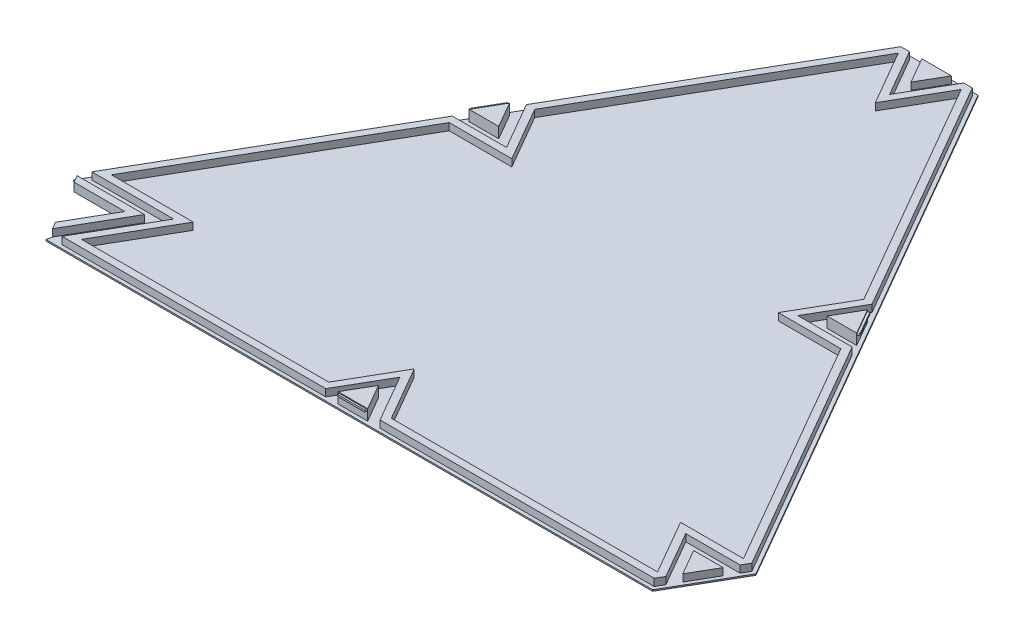
SolidWorks part; units mm, degrees
ref_plane "Front Plane" through (0, 0, 0) normal (0, 0, 1) x (1, 0, 0)
ref_plane "Top Plane" through (0, 0, 0) normal (0, 1, 0) x (1, 0, 0)
ref_plane "Right Plane" through (0, 0, 0) normal (1, 0, 0) x (0, 0, -1)
sketch "Sketch1" plane through (0, 0, 0) normal (0, 1, 0) x (1, 0, 0)
  line L17 (-84.5662, 18.8923) -> (-84.5662, 18.3923) construction
  line L24 (-89.7106, 9.9821) -> (-89.2776, 10.2321) construction
  line L25 (-79.4219, 9.9821) -> (-79.8549, 10.2321) construction
  line L27 (-84.5662, 2.0718) -> (-75.1436, 18.3923)
  line L28 (-93.9889, 18.3923) -> (-75.1436, 18.3923)
  line L29 (-2.5, 5.4019) -> (-2.067, 5.1519) construction
  line L58 (2.5, 5.4019) -> (2.067, 5.1519) construction
  line L59 (0, 1.0718) -> (0, 1.5718) construction
  line L65 (-4.134, 1.5718) -> (4.134, 1.5718)
  line L69 (0, 8.7321) -> (4.134, 1.5718)
  line L71 (-4.134, 1.5718) -> (0, 8.7321)
  line L79 (87.2106, 14.3122) -> (87.2106, 13.8122) construction
  line L81 (84.7106, 9.9821) -> (85.1436, 10.2321) construction
  line L135 (89.7106, 9.9821) -> (89.2776, 10.2321) construction
  line L138 (83.0766, 13.8122) -> (91.3446, 13.8122)
  line L146 (87.2106, 6.6519) -> (91.3446, 13.8122)
  line L149 (83.0766, 13.8122) -> (87.2106, 6.6519)
  line L157 (47.5718, 92.1288) -> (48.0048, 91.8788) construction
  line L158 (52.5718, 92.1288) -> (52.1388, 91.8788) construction
  line L160 (50.0718, 87.7987) -> (50.0718, 88.2987) construction
  line L161 (45.9378, 88.2987) -> (54.2058, 88.2987)
  line L162 (50.0718, 95.4589) -> (54.2058, 88.2987)
  line L163 (45.9378, 88.2987) -> (50.0718, 95.4589)
  line L164 (0, 165.3653) -> (0, 164.8653) construction
  line L165 (-2.5, 161.0352) -> (-2.067, 161.2852) construction
  line L166 (2.5, 161.0352) -> (2.067, 161.2852) construction
  line L167 (-4.134, 164.8653) -> (4.134, 164.8653)
  line L168 (0, 157.7051) -> (4.134, 164.8653)
  line L169 (-4.134, 164.8653) -> (0, 157.7051)
  line L170 (-52.5718, 92.1288) -> (-52.1388, 91.8788) construction
  line L171 (-47.5718, 92.1288) -> (-48.0048, 91.8788) construction
  line L172 (-50.0718, 87.7987) -> (-50.0718, 88.2987) construction
  line L173 (-54.2058, 88.2987) -> (-45.9378, 88.2987)
  line L174 (-50.0718, 95.4589) -> (-45.9378, 88.2987)
  line L175 (-54.2058, 88.2987) -> (-50.0718, 95.4589)
  line L176 (-76.5352, 10.9821) -> (-76.1021, 10.7321) construction
  line L177 (-69.9474, 21.3923) -> (-81.3908, 1.5718)
  line L178 (-3.6547, 7.4019) -> (-4.0877, 7.6519) construction
  line L179 (0, 14.7321) -> (-7.5981, 1.5718)
  line L180 (-7.5981, 1.5718) -> (-81.3908, 1.5718)
  line L181 (3.6547, 7.4019) -> (4.0877, 7.6519) construction
  line L182 (82.4012, 9.9821) -> (81.9682, 9.7321) construction
  line L183 (0, 14.7321) -> (7.5981, 1.5718)
  line L184 (85.3111, 2.3619) -> (84.878, 2.6119) construction
  line L185 (7.5981, 1.5718) -> (84.2776, 1.5718)
  line L186 (85.4785, 3.6519) -> (84.2776, 1.5718)
  line L187 (77.8805, 16.8122) -> (85.4785, 3.6519)
  line L188 (86.0559, 16.3122) -> (86.0559, 16.8122) construction
  line L189 (94.1101, 17.6022) -> (93.6771, 17.8522) construction
  line L190 (77.8805, 16.8122) -> (93.0766, 16.8122)
  line L191 (94.2776, 18.8923) -> (93.0766, 16.8122)
  line L192 (75.5407, 52.3455) -> (75.1077, 52.0955) construction
  line L193 (55.9378, 85.2987) -> (94.2776, 18.8923)
  line L194 (48.3397, 85.2987) -> (48.3397, 83.2987) construction
  line L195 (40.7417, 85.2987) -> (55.9378, 85.2987)
  line L196 (45.2624, 92.1288) -> (44.8294, 92.3788) construction
  line L197 (29.6029, 131.9121) -> (29.1699, 131.6621) construction
  line L198 (10, 164.8653) -> (48.3397, 98.4589)
  line L199 (40.7417, 85.2987) -> (48.3397, 98.4589)
  line L200 (8.799, 165.3653) -> (8.799, 164.8653) construction
  line L201 (7.5981, 164.8653) -> (10, 164.8653)
  line L202 (3.6547, 159.0352) -> (4.0877, 158.7852) construction
  line L203 (7.5981, 164.8653) -> (0, 151.7051)
  line L204 (-8.799, 165.3653) -> (-8.799, 164.8653) construction
  line L205 (-3.6547, 159.0352) -> (-4.0877, 158.7852) construction
  line L206 (-29.6029, 131.9121) -> (-29.1699, 131.6621) construction
  line L207 (-48.3397, 98.4589) -> (-10, 164.8653)
  line L208 (-10, 164.8653) -> (-7.5981, 164.8653)
  line L209 (0, 151.7051) -> (-7.5981, 164.8653)
  line L210 (-45.2624, 92.1288) -> (-44.8294, 92.3788) construction
  line L211 (-48.3397, 98.4589) -> (-40.7417, 85.2987)
  line L212 (-48.3397, 85.2987) -> (-48.3397, 83.2987) construction
  line L213 (-74.9634, 53.3455) -> (-74.5303, 53.0955) construction
  line L214 (-92.8342, 21.3923) -> (-55.9378, 85.2987)
  line L215 (-55.9378, 85.2987) -> (-40.7417, 85.2987)
  line L216 (-82.2568, 20.8923) -> (-82.2568, 21.3923) construction
  line L217 (-92.8342, 21.3923) -> (-69.9474, 21.3923)
  line L218 (-44.7831, 1.0718) -> (-44.7831, 0.5718) construction
  line L219 (-84.8549, 0.5718) -> (84.8549, 0.5718)
  line L220 (-89.7106, 9.9821) -> (-90.1436, 9.7321) construction
  line L222 (0, 165.3653) -> (0, 165.8653) construction
  line L223 (10.5774, 165.8653) -> (-10.5774, 165.8653)
  line L224 (-95.4323, 18.8923) -> (-10.5774, 165.8653)
  line L225 (52.5718, 92.1288) -> (53.0048, 92.3788) construction
  line L226 (95.4323, 18.8923) -> (10.5774, 165.8653)
  line L227 (89.7106, 9.9821) -> (90.1436, 9.7321) construction
  line L228 (84.8549, 0.5718) -> (95.4323, 18.8923)
  line L229 (-84.5662, 18.3923) -> (-84.5662, 16.3923) construction
  line L230 (-79.8549, 10.2321) -> (-81.587, 11.2321) construction
  line L232 (-89.2776, 10.2321) -> (-87.5455, 11.2321) construction
  line L235 (-95.4323, 18.8923) -> (-93.9889, 18.3923)
  line L236 (-84.8549, 0.5718) -> (-84.5662, 2.0718)
  line L238 (-92.8342, 16.3923) -> (-78.6077, 16.3923)
  line L239 (-78.6077, 16.3923) -> (-85.7209, 4.0718)
  line L240 (-93.9889, 18.3923) -> (-92.8342, 16.3923)
  line L241 (-85.7209, 4.0718) -> (-84.5662, 2.0718)
  line L242 (-44.4944, 1.5718) -> (-44.4944, 3.5718) construction
  line L243 (-75.6691, 11.4821) -> (-73.9371, 10.4821) construction
  line L244 (-77.9267, 3.5718) -> (-66.4833, 23.3923)
  line L245 (-77.9267, 3.5718) -> (-8.7528, 3.5718)
  line L246 (-3.799, 8.1519) -> (-5.5311, 9.1519) construction
  line L247 (-8.7528, 3.5718) -> (0, 18.7321)
  line L248 (4.0877, 7.6519) -> (5.8198, 8.6519) construction
  line L249 (45.9378, 1.5718) -> (45.9378, 3.5718) construction
  line L250 (0, 18.7321) -> (8.7528, 3.5718)
  line L251 (81.9682, 9.7321) -> (80.2361, 8.7321) construction
  line L252 (45.9378, 3.5718) -> (8.7528, 3.5718)
  line L253 (74.4164, 18.8122) -> (83.2154, 3.5718)
  line L254 (45.9378, 3.5718) -> (83.2154, 3.5718)
  line L255 (85.4785, 16.8122) -> (85.4785, 18.8122) construction
  line L256 (74.4164, 18.8122) -> (92.0144, 18.8122)
  line L257 (75.1077, 52.0955) -> (73.3756, 51.0955) construction
  line L258 (44.8294, 92.3788) -> (43.0973, 93.3788) construction
  line L259 (54.7831, 83.2987) -> (92.0144, 18.8122)
  line L260 (54.7831, 83.2987) -> (37.2776, 83.2987)
  line L261 (46.0303, 98.4589) -> (37.2776, 83.2987)
  line L262 (29.1699, 131.6621) -> (27.4378, 130.6621) construction
  line L263 (46.0303, 98.4589) -> (8.799, 162.9455)
  line L264 (4.0877, 158.7852) -> (5.8198, 157.7852) construction
  line L265 (0, 147.7051) -> (8.799, 162.9455)
  line L266 (-3.218, 157.2789) -> (-4.9501, 156.2789) construction
  line L267 (-8.799, 162.9455) -> (0, 147.7051)
  line L268 (-29.1699, 131.6621) -> (-27.4378, 130.6621) construction
  line L269 (-8.799, 162.9455) -> (-46.0303, 98.4589)
  line L270 (-44.5407, 91.8788) -> (-42.8087, 92.8788) construction
  line L271 (-46.0303, 98.4589) -> (-37.2776, 83.2987)
  line L272 (-54.7831, 83.2987) -> (-37.2776, 83.2987)
  line L273 (-72.465, 56.6729) -> (-70.7329, 55.6729) construction
  line L274 (-54.7831, 83.2987) -> (-89.3701, 23.3923)
  line L275 (-81.3908, 21.3923) -> (-81.3908, 23.3923) construction
  line L276 (-89.3701, 23.3923) -> (-66.4833, 23.3923)
  point P9 (-89.2776, 10.2321)
  point P12 (-79.8549, 10.2321)
  point P15 (-84.5662, 18.3923)
  point P21 (0, 1.5718)
  point P24 (2.067, 5.1519)
  point P27 (-2.067, 5.1519)
  point P32 (87.2106, 13.8122)
  point P36 (89.2776, 10.2321)
  point P41 (85.1436, 10.2321)
  point P48 (50.0718, 88.2987)
  point P49 (-84.5662, 16.3923)
  point P51 (50.0718, 88.2987)
  point P54 (52.1388, 91.8788)
  point P58 (48.0048, 91.8788)
  point P64 (-81.587, 11.2321)
  point P68 (-87.5455, 11.2321)
  point P74 (0, 164.8653)
  point P76 (-73.9371, 10.4821)
  point P81 (-44.4944, 3.5718)
  point P84 (-5.5311, 9.1519)
  point P87 (5.8198, 8.6519)
  point P89 (2.067, 161.2852)
  point P95 (80.2361, 8.7321)
  point P97 (-2.067, 161.2852)
  point P105 (85.4785, 18.8122)
  point P106 (-50.0718, 88.2987)
  point P109 (-50.0718, 88.2987)
  point P114 (-48.0048, 91.8788)
  point P118 (48.3397, 83.2987)
  point P119 (-52.1388, 91.8788)
  point P123 (-76.1021, 10.7321)
  point P131 (-4.0877, 7.6519)
  point P138 (4.0877, 7.6519)
  point P144 (84.878, 2.6119)
  point P146 (81.9682, 9.7321)
  point P151 (86.0559, 16.8122)
  point P154 (93.6771, 17.8522)
  point P156 (75.1077, 52.0955)
  point P157 (27.4378, 130.6621)
  point P168 (44.8294, 92.3788)
  point P172 (8.799, 164.8653)
  point P176 (4.0877, 158.7852)
  point P184 (-8.799, 164.8653)
  point P187 (-29.1699, 131.6621)
  point P191 (-44.8294, 92.3788)
  point P198 (-74.5303, 53.0955)
  point P204 (-82.2568, 21.3923)
  point P208 (-90.1436, 9.7321)
  point P212 (0, 165.8653)
  point P214 (0, 165.8653)
  point P217 (53.0048, 92.3788)
  point P218 (5.8198, 157.7852)
  point P220 (90.1436, 9.7321)
  point P226 (-27.4378, 130.6621)
  point P230 (-42.8087, 92.8788)
  point P231 (-42.8087, 92.8788)
  point P237 (-81.3908, 23.3923)
  dimension "D1" = 0.5
  dimension "D2" = 0.5
extrude "Boss-Extrude1" add sketch "Sketch1" along normal blind 2.38 contours L214 L217 L177 L180 L179 L183 L185 L186 L187 L190 L191 L193 L195 L199 L198 L201 L203 L209 L208 L207 L211 L215 | L239 L241 L27 L28 L240 L238 | L138 L146 L149 | L167 L168 L169 region at (-84.9277, 0, -3.1964) region at (-81.3908, 0, -21.6407)
extrude "Boss-Extrude4" add sketch "Sketch1<8>" along normal blind 0.38 contours L219 L228 L226 L223 L224 L173 L175 L174 L161 L163 L162 L65 L71 L69 L28 L27 L149 L138 L146 L169 L167 L168 L217 L214 L215 L211 L207 L208 L209 L203 L201 L198 L199 L195 L193 L191 L190 L187 L186 L185 L183 L179 | L276 L244 L245 L247 L250 L252 L254 L253 L256 L259 L260 L261 L263 L265 L267 L269 L271 L272 L274 region at (-77.6683, 0, -8.9696)
sketch "Sketch1<8>" plane through (0, 0, 0) normal (0, 1, 0) x (1, 0, 0) same geometry as "Sketch1"
extrude "Boss-Extrude5" add sketch "Sketch1<9>" along normal blind 3.38 contours L175 L173 L174 | L71 L65 L69 | L163 L161 L162 region at (0, 0, -3.9585) region at (50.0718, 0, -90.6854) region at (-50.0718, 0, -90.6854)
sketch "Sketch1<9>" plane through (0, 0, 0) normal (0, 1, 0) x (1, 0, 0) same geometry as "Sketch1"
sketch "Sketch2" plane through (0, 0, -1.5718) normal (0, 0, 1) x (1, 0, 0)
  line L0 (-4.134, 3.38) -> (4.134, 2.38) construction
  line L3 (-4.134, 2.38) -> (4.134, 2.38) construction
  line L4 (4.134, 2.38) -> (4.134, 3.38) construction
  line L5 (4.134, 3.38) -> (-4.134, 2.38) construction
  line L6 (3.75, 2.88) -> (-3.75, 2.88) construction
  line L7 (3.75, 2.63) -> (-3.75, 2.63)
  line L8 (3.75, 3.13) -> (-3.75, 3.13)
  arc A0 (3.75, 2.63) -> (3.75, 3.13) centre (3.75, 2.88) ccw
  arc A1 (-3.75, 3.13) -> (-3.75, 2.63) centre (-3.75, 2.88) ccw
  point P4 (0, 2.88)
extrude "Boss-Extrude6" add sketch "Sketch2" along normal blind 0.5
sketch "Sketch4" plane through (-78.8888, 0, -45.5465) normal (-0.866, 0, -0.5) x (-0.5, 0, 0.866)
  line L0 (-57.634, 2.38) -> (-49.366, 2.38) construction
  line L1 (-53.5, 3.38) -> (-53.5, 2.38) construction
  line L2 (-49.366, 3.38) -> (-57.634, 3.38) construction
  line L3 (-57.25, 2.88) -> (-49.75, 2.88) construction
  line L4 (-57.25, 3.1419) -> (-49.75, 3.1419)
  line L5 (-57.25, 2.6181) -> (-49.75, 2.6181)
  arc A0 (-57.25, 3.1419) -> (-57.25, 2.6181) centre (-57.25, 2.88) ccw
  arc A1 (-49.75, 2.6181) -> (-49.75, 3.1419) centre (-49.75, 2.88) ccw
  point P10 (-53.5, 2.88)
extrude "Boss-Extrude7" add sketch "Sketch4" along normal blind 0.6
sketch "Sketch5" plane through (78.8888, 0, -45.5465) normal (0.866, 0, -0.5) x (-0.5, 0, -0.866)
  line L0 (49.366, 2.38) -> (57.634, 2.38) construction
  line L1 (53.5, 2.38) -> (45.9019, 2.38) construction
  line L2 (49.366, 3.38) -> (49.366, 0.38) construction
  line L3 (57.634, 3.38) -> (57.634, 0.38) construction
  line L4 (53.5, 2.38) -> (61.0981, 2.38) construction
  line L5 (53.5, 3.38) -> (53.5, 2.38) construction
  line L6 (57.634, 3.38) -> (49.366, 3.38) construction
  line L7 (49.75, 2.88) -> (57.25, 2.88) construction
  line L8 (49.75, 3.13) -> (57.25, 3.13)
  line L9 (49.75, 2.63) -> (57.25, 2.63)
  arc A0 (49.75, 3.13) -> (49.75, 2.63) centre (49.75, 2.88) ccw
  arc A1 (57.25, 2.63) -> (57.25, 3.13) centre (57.25, 2.88) ccw
  point P16 (53.5, 2.88)
extrude "Boss-Extrude8" add sketch "Sketch5" along normal blind 0.6
